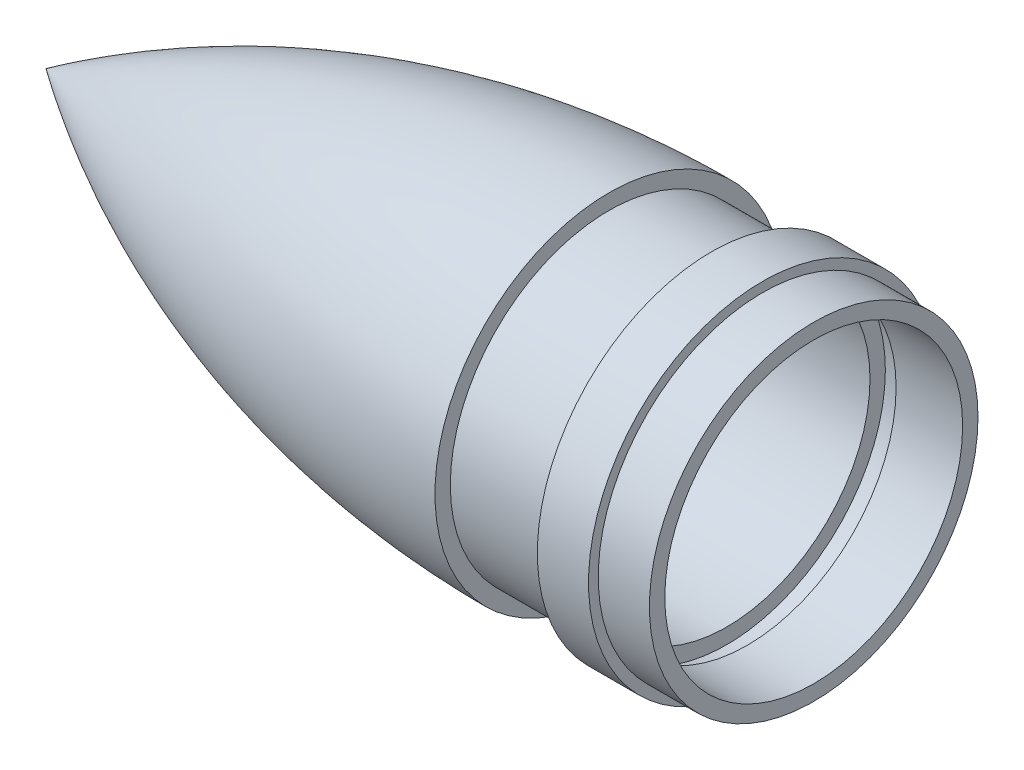
SolidWorks part; units mm, degrees
material "ABS"
ref_plane "Front Plane" through (0, 0, 0) normal (0, 0, 1) x (1, 0, 0)
ref_plane "Top Plane" through (0, 0, 0) normal (0, 1, 0) x (1, 0, 0)
ref_plane "Right Plane" through (0, 0, 0) normal (1, 0, 0) x (0, 0, -1)
sketch "Sketch2" plane through (0, 0, 0) normal (0, 0, 1) x (1, 0, 0)
  line L0 (0, 194.94) -> (0, 160.94)
  line L1 (0, 160.94) -> (-109.9996, 160.94)
  arc A0 (0, 194.94) -> (-109.9996, 160.94) centre (0, 0) ccw
  dimension "D1" = 389.88
  dimension "D2" = 34
  dimension "D3" = 109.9996
revolve "Revolve1" add sketch "Sketch2" angle 360 about L1
sketch "Sketch3" plane through (0, 0, 0) normal (1, 0, 0) x (0, 0, -1)
  circle A0 centre (0, 160.94) radius 31
  dimension "D1" = 62
extrude "Boss-Extrude1" add sketch "Sketch3" along normal blind 20
sketch "Sketch4" plane through (20, 0, 0) normal (1, 0, 0) x (0, 0, -1)
  circle A0 centre (0, 160.94) radius 34
  dimension "D1" = 68
extrude "Boss-Extrude2" add sketch "Sketch4" along normal blind 10
sketch "Sketch5" plane through (30, 0, 0) normal (1, 0, 0) x (0, 0, -1)
  circle A0 centre (0, 160.94) radius 32.1
  dimension "D1" = 64.2
extrude "Boss-Extrude3" add sketch "Sketch5" along normal blind 10
shell "Shell1" thickness 3 removed face at (40, 160.94, -32.1)
